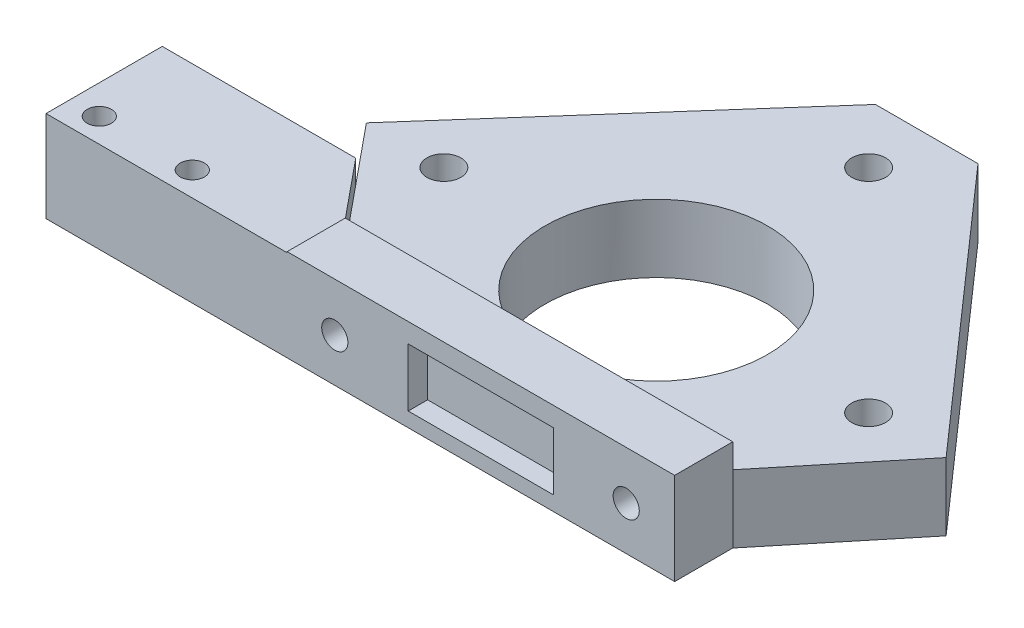
SolidWorks part; units mm, degrees
ref_plane "Front Plane" through (0, 0, 0) normal (0, 0, 1) x (1, 0, 0)
ref_plane "Top Plane" through (0, 0, 0) normal (0, 1, 0) x (1, 0, 0)
ref_plane "Right Plane" through (0, 0, 0) normal (1, 0, 0) x (0, 0, -1)
sketch "Sketch1" plane through (0, 0, 0) normal (0, 0, 1) x (1, 0, 0)
  line L0 (0, 5) -> (40, 5) construction
  line L1 (0, 0) -> (40, 0)
  line L2 (0, 0) -> (0, 10)
  line L3 (0, 10) -> (40, 10)
  line L4 (40, 0) -> (40, 10)
  line L6 (12.5, 2) -> (27.5, 2)
  line L7 (12.5, 2) -> (12.5, 8)
  line L8 (12.5, 8) -> (27.5, 8)
  line L9 (27.5, 2) -> (27.5, 8)
  line L10 (12.5, 2) -> (27.5, 8) construction
  line L11 (12.5, 8) -> (27.5, 2) construction
  circle A0 centre (5, 5) radius 1.5
  circle A1 centre (35, 5) radius 1.5
  point P11 (20, 5)
  dimension "D1" = 30
  dimension "D3" = 5
  dimension "D4" = 3
  dimension "D2" = 40
  dimension "D5" = 10
  dimension "D6" = 6
  dimension "D7" = 15
extrude "Boss-Extrude1" add sketch "Sketch1" along normal blind 6
extrude "Boss-Extrude2" add sketch "Sketch1<3>" along normal blind 4 contours L6 L9 L8 L7 region at (20, 5, 0)
sketch "Sketch1<3>" plane through (0, 0, 0) normal (0, 0, 1) x (1, 0, 0) same geometry as "Sketch1"
sketch "Sketch2" plane through (0, 10, 0) normal (0, 1, 0) x (1, 0, 0)
  line L0 (40, 0) -> (0, 0) construction
  line L1 (8, 0) -> (8, 12.1)
  line L2 (32, 0) -> (32, 12.1)
  line L3 (8, 0) -> (32, 0)
  line L4 (-1.9203, 12.1) -> (20, 34.0203) construction
  line L5 (20, 34.0203) -> (41.9203, 12.1) construction
  line L6 (41.9203, 12.1) -> (20, -9.8203) construction
  line L7 (20, -9.8203) -> (-1.9203, 12.1) construction
  line L8 (-1.9203, 12.1) -> (41.9203, 12.1) construction
  line L9 (0, 0) -> (-9.9203, 12.1)
  line L10 (-9.9203, 12.1) -> (14.7085, 40.0203)
  line L11 (14.7085, 40.0203) -> (25.2915, 40.0203)
  line L12 (25.2915, 40.0203) -> (49.9203, 12.1)
  line L13 (49.9203, 12.1) -> (40, 0)
  line L14 (40, -6) -> (40, 0) construction
  line L15 (20, 0) -> (20, 40.0203) construction
  circle A0 centre (20, 12.1) radius 11.5
  arc A1 (32, 12.1) -> (8, 12.1) centre (20, 12.1) ccw
  circle A2 centre (-1.9203, 12.1) radius 1.75
  circle A3 centre (20, 34.0203) radius 1.75
  circle A4 centre (41.9203, 12.1) radius 1.75
  point P5 (20, 0)
  line M2 (40, 0) -> (0, 0)
  dimension "D1" = 23
  dimension "D2" = 12
  dimension "D5" = 3.5
  dimension "D3" = 12.1
  dimension "D4" = 31
  dimension "D6" = 6
  dimension "D7" = 8
  dimension "D8" = 8
extrude "Boss-Extrude3" add sketch "Sketch2" against normal blind 5 from offset 2.5 contours A1 L2 L13 L12 L11 L10 L9 L1 A4 A3 A2 M2 | L2 A1 L1 A0 M2 region at (4, 10, -0.7199) region at (8.3401, 10, -6.05) offset against normal yes
sketch "Sketch3" plane through (0, 0, 0) normal (0, 1, 0) x (1, 0, 0)
  line L1 (0, -6) -> (40, -6)
  line L2 (0, -6) -> (0, 0)
  line L3 (0, 0) -> (40, 0)
  line L4 (40, -6) -> (40, 0)
extrude "Cut-Extrude1" cut sketch "Sketch3" along normal blind 0.5
extrude "Boss-Extrude4" add sketch "Sketch2<3>" along normal up to surface (-7.5 mm away) from surface contours A1 L2 L13 L12 L11 L10 L9 L1 A4 A3 A2 M2 | L2 A1 L1 A0 M2 region at (4, 10, -0.7199) region at (8.3401, 10, -6.05) up to face at (41.9203, 2.5, -10.35) starting at face at (20, 0.5, 3)
sketch "Sketch2<3>" plane through (0, 10, 0) normal (0, 1, 0) x (1, 0, 0) same geometry as "Sketch2"
sketch "Sketch4" plane through (0, 7.5, 0) normal (0, 1, 0) x (1, 0, 0)
  line L1 (-9.9203, 12.1) -> (14.7085, 40.0203) construction
  line L2 (-25.8865, -6) -> (-24.8915, -6)
  line L3 (-24.8915, -6) -> (-24.8915, 6)
  line L4 (-24.8915, 6) -> (-15.3012, 6)
  line L6 (-15.3012, 6) -> (-4.9192, 6)
  line L7 (0, 0) -> (-9.9203, 12.1) construction
  line L8 (-4.9192, 6) -> (4.9192, -6)
  line L9 (4.9192, -6) -> (-25.8865, -6)
  circle A0 centre (-21.8915, -3.5) radius 1.25
  circle A1 centre (-12.2915, -3.5) radius 1.25
  line M10 (-9.9203, 12.1) -> (0, 0)
  line M15 (14.7085, 40.0203) -> (-9.9203, 12.1)
  dimension "D4" = 2.5
  dimension "D5" = 7.1
  dimension "D6" = 27
  dimension "D1" = 2.5
  dimension "D2" = 12
  dimension "D3" = 3
extrude "Boss-Extrude5" add sketch "Sketch4" against normal up to surface (7 mm away) contours L4 L3 L2 A1 A0 M15 region at (-12.1203, 7.5, 0.2897) up to face at (20, 0.5, -11.5301)
extrude "Boss-Extrude6" add sketch "Sketch4<3>" along normal blind 2.4 contours L9 L8 L6 L4 L3 A1 A0 M10 region at (-12.1203, 7.5, 0.2897)
sketch "Sketch4<3>" plane through (0, 7.5, 0) normal (0, 1, 0) x (1, 0, 0) same geometry as "Sketch4"
sketch "Sketch5" plane through (0, 0, 6) normal (0, 0, 1) x (1, 0, 0)
  line L0 (4.9192, 3.5022) -> (4.9192, 6.4978) construction
  circle A0 centre (35, 5) radius 1.35
  circle A1 centre (4.9192, 5) radius 1.35
  circle A4 centre (4.9192, 5) radius 2.9022
  circle A5 centre (35, 5) radius 2.7558
  line M8 (4.9192, 3.5022) -> (4.9192, 6.4978)
  dimension "D1" = 2.7
  dimension "D2" = 2.7
extrude "Boss-Extrude7" add sketch "Sketch5" against normal up to surface (6 mm away) up to face at (16, 8.98, 0)
extrude "Cut-Extrude2" cut sketch "Sketch5<2>" against normal blind 16 and the other way through all contours A1 M8 | A1 M8 | A0 region at (35, 5, 6) region at (5.4921, 5, 6) region at (4.3462, 5, 6)
sketch "Sketch5<2>" plane through (0, 0, 6) normal (0, 0, 1) x (1, 0, 0) same geometry as "Sketch5"
